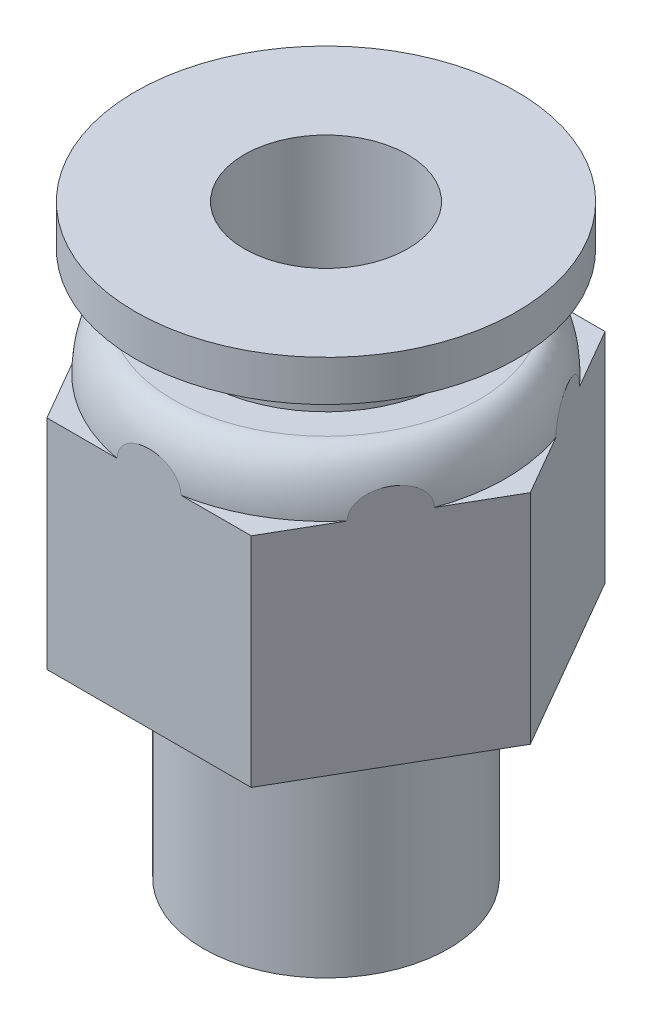
SolidWorks part; units mm, degrees
ref_plane "Front Plane" through (0, 0, 0) normal (0, 0, 1) x (1, 0, 0)
ref_plane "Top Plane" through (0, 0, 0) normal (0, 1, 0) x (1, 0, 0)
ref_plane "Right Plane" through (0, 0, 0) normal (1, 0, 0) x (0, 0, -1)
sketch "Sketch1" plane through (0, 0, 0) normal (0, 0, 1) x (1, 0, 0)
  line L0 (0, 22.6127) -> (0, -32.3083) construction
  line L1 (0, 10) -> (6.6, 10)
  line L2 (6.6, 10) -> (6.6, 8)
  line L3 (6.6, 8) -> (7.5, 8)
  line L4 (7.5, 8) -> (7.5, 0)
  line L5 (7.5, 0) -> (4.5, 0)
  line L6 (4.5, 0) -> (4.5, -8)
  line L7 (4.5, -8) -> (0, -8)
  line L8 (0, 10) -> (0, -8)
  point P5 (0, 0)
  point P12 (5.5862, 10)
  dimension "D1" = 4.5
  dimension "D2" = 8
  dimension "D3" = 8
  dimension "D4" = 2
  dimension "D5" = 7.5
  dimension "D6" = 6.6
revolve "Revolve1" add sketch "Sketch1" angle 360 about L0
fillet "Fillet1" radius 2 1 edges at (0, 10, 6.6) second distance 1 first distance on face at (0, 10, 6.6)
sketch "Sketch2" plane through (0, 8, 0) normal (0, 1, 0) x (1, 0, 0)
  line L0 (0, 0) -> (7.5, 0) construction
  line L1 (0, 0) -> (3.75, 6.4952) construction
  line L2 (3.75, 6.4952) -> (7.5, 0)
  circle A0 centre (0, 0) radius 7.5 construction
  arc A1 (7.5, 0) -> (3.75, 6.4952) centre (0, 0) ccw
  dimension "D1" = 60
extrude "Cut-Extrude1" cut sketch "Sketch2" against normal through all and the other way through all
pattern_circular "CirPattern1" count 6 over 360 about axis through (0, 22.6127, 0) along (0, 1, 0) of "Cut-Extrude1" reverse direction yes
sketch "Sketch6" plane through (0, -8, 0) normal (0, -1, 0) x (1, 0, 0)
  circle A0 centre (0, 0) radius 3
  dimension "D1" = 6
extrude "Cut-Extrude2" cut sketch "Sketch6" against normal through all
sketch "Sketch7" plane through (0, 0, 0) normal (0, 0, 1) x (1, 0, 0)
  line L0 (3, 10) -> (3, 13.5)
  line L1 (3, 13.5) -> (7, 13.5)
  line L2 (7, 13.5) -> (7, 12)
  line L3 (7, 12) -> (4.5, 12)
  line L4 (4.5, 12) -> (4.5, 10)
  line L5 (5.6, 10) -> (-5.6, 10) construction
  line L6 (4.5, 10) -> (3, 10)
  dimension "D1" = 4
  dimension "D2" = 1.5
  dimension "D3" = 2.5
  dimension "D4" = 3.5
revolve "Revolve2" add sketch "Sketch7" angle 360 about axis through (0, 10.01, 0) along (0, -1, 0)
